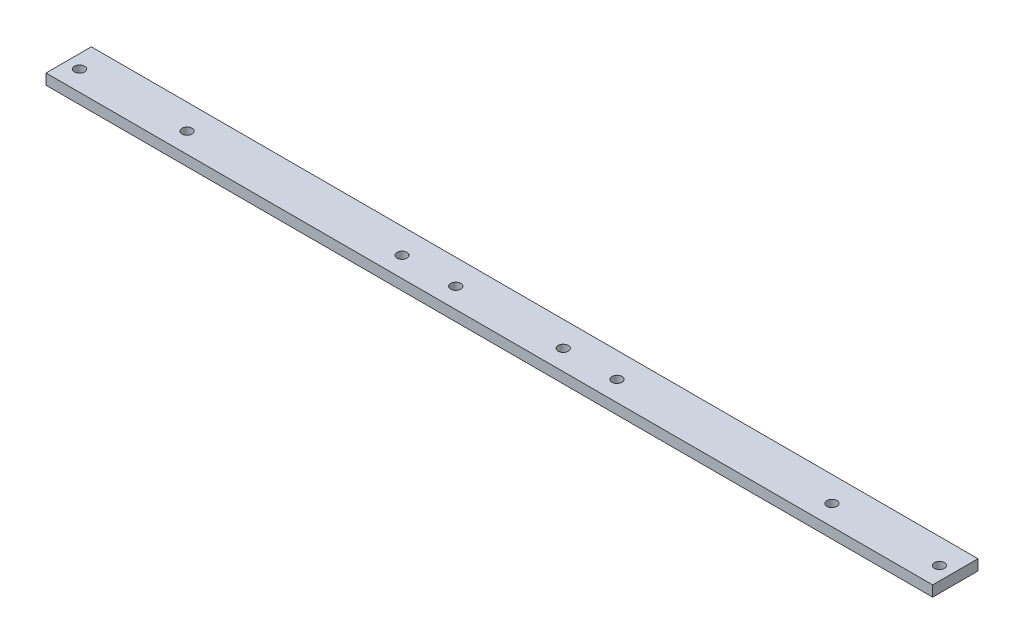
SolidWorks part; units mm, degrees
ref_plane "Front" through (0, 0, 0) normal (0, 0, 1) x (1, 0, 0)
ref_plane "Top" through (0, 0, 0) normal (0, 1, 0) x (1, 0, 0)
ref_plane "Right" through (0, 0, 0) normal (1, 0, 0) x (0, 0, -1)
sketch "Sketch1" plane through (0, 0, 0) normal (0, 1, 0) x (1, 0, 0)
  line L0 (0, 25.5356) -> (0, -1.4644)
  line L3 (0, 25.5356) -> (264, 25.5356)
  line L7 (0, -1.4644) -> (264, -1.4644)
  line L8 (264, -1.4644) -> (264, 25.5356)
  line L9 (264, -1.4644) -> (264, 10.5356)
  line L10 (264, 21.5356) -> (260, 21.5356)
  line L11 (0, 21.5356) -> (4, 21.5356)
  line L12 (4, 21.5356) -> (260, 21.5356)
  line L13 (4, 21.5356) -> (132, 21.5356)
  line L14 (132, 21.5356) -> (260, 21.5356)
  line L15 (264, 10.5356) -> (264, -1.4644)
  line L16 (264, 4.5356) -> (260, 4.5356)
  line L17 (132, 25.5356) -> (132, 23.5356)
  line L18 (4, 21.5356) -> (68, 21.5356)
  line L19 (68, 21.5356) -> (36, 21.5356)
  line L20 (36, 21.5356) -> (36, 4.5356)
  line L21 (196, 21.5356) -> (260, 21.5356)
  line L22 (228, 21.5356) -> (228, 4.5356)
  line L23 (132, 21.5356) -> (132, 4.5356)
  line L24 (132, 21.5356) -> (164, 21.5356)
  circle A0 centre (4, 21.5356) radius 2
  circle A1 centre (260, 21.5356) radius 2
  circle A2 centre (132, 21.5356) radius 2
  circle A3 centre (68, 21.5356) radius 2
  circle A4 centre (196, 21.5356) radius 2
  circle A5 centre (260, 4.5356) radius 1.5
  circle A6 centre (4, 4.5356) radius 1.5
  circle A7 centre (36, 4.5356) radius 1.5
  circle A8 centre (228, 4.5356) radius 1.5
  circle A9 centre (132, 4.5356) radius 1.5
  circle A10 centre (164, 21.5356) radius 2
  circle A11 centre (100, 21.5356) radius 2
  dimension "D5" = 23
  dimension "D6" = 128
  dimension "D9" = 4
  dimension "D10" = 32
  dimension "D1" = 4
  dimension "D2" = 264
  dimension "D3" = 4
  dimension "D4" = 4
  dimension "D7" = 128
  dimension "D8" = 12
extrude "Boss-Extrude1" add sketch "Sketch1" along normal blind 3.175 contours A1 L10 L3 A0 | A1 A0 L10 | A3 L13 A2 L17 L3 L0 L11 A0 | A9 | A0 | A1 region at (65.9183, 0, -23.5857) region at (1, 0, -18.8856) region at (198.0817, 0, -23.5857)
sketch "Sketch2" plane through (0, 3.175, 0) normal (0, 1, 0) x (1, 0, 0)
  line L0 (37.5, 4.5356) -> (228, 4.5356)
  line L1 (132, 21.5356) -> (132, 4.5356)
  line L2 (132, 4.5356) -> (148, 4.5356)
  line L3 (148, 4.5356) -> (116, 4.5356)
  line L4 (116, 4.5356) -> (100, 4.5356)
  line L5 (148, 4.5356) -> (164, 4.5356)
  circle A0 centre (36, 4.5356) radius 1.5 construction
  circle A1 centre (116, 4.5356) radius 1.5
  circle A2 centre (148, 4.5356) radius 1.5
  circle A3 centre (100, 4.5356) radius 1.5
  circle A4 centre (164, 4.5356) radius 1.5
  dimension "D3" = 16
  dimension "D1" = 16
  dimension "D2" = 16
  dimension "D4" = 16
extrude "Cut-Extrude1" cut sketch "Sketch2" against normal blind 10 contours A3 | A1 | A2 | A4
sketch "Sketch3" plane through (0, 3.175, 0) normal (0, 1, 0) x (1, 0, 0)
  line L0 (264, -1.4644) -> (264, 25.5356) construction
  line L1 (0, 25.5356) -> (264, 25.5356)
  line L2 (0, 25.5356) -> (0, 12.0356)
  line L3 (0, 12.0356) -> (264, 12.0356)
  line L4 (264, 25.5356) -> (264, 12.0356)
extrude "Cut-Extrude2" cut sketch "Sketch3" against normal blind 10
